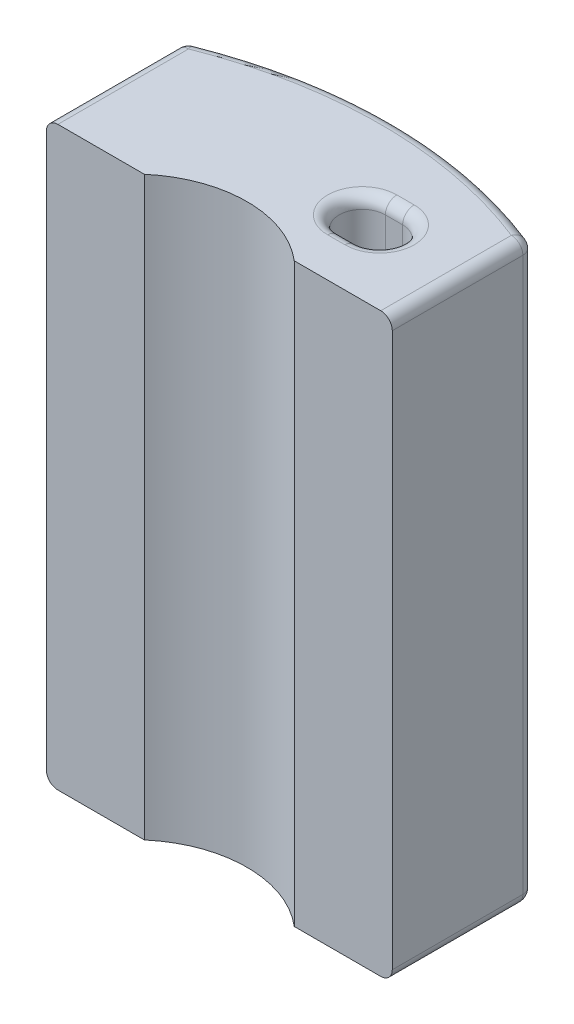
SolidWorks part; units mm, degrees
ref_plane "Front Plane" through (0, 0, 0) normal (0, 0, 1) x (1, 0, 0)
ref_plane "Top Plane" through (0, 0, 0) normal (0, 1, 0) x (1, 0, 0)
ref_plane "Right Plane" through (0, 0, 0) normal (1, 0, 0) x (0, 0, -1)
sketch "Sketch1" plane through (0, 0, 0) normal (0, 1, 0) x (1, 0, 0)
  line L0 (-15, 2) -> (15, 2) construction
  line L1 (-15, 2) -> (-15, -10)
  line L2 (-15, -10) -> (-6.4992, -10)
  line L3 (15, 2) -> (15, -10)
  line L4 (15, -10) -> (6.4992, -10)
  line L5 (0, 0) -> (0, -17.6) construction
  line L6 (-8.9, 0) -> (8.9, 0) construction
  line L7 (-8.9, 0) -> (-8.9, -1.6) construction
  line L8 (-8.9, -1.6) -> (8.9, -1.6) construction
  line L9 (8.9, 0) -> (8.9, -1.6) construction
  line L10 (0, 0) -> (0, 5) construction
  line L11 (-9.5, 2) -> (-9.5, -4.6) construction
  line L12 (-9.5, -4.6) -> (-7, -4.6) construction
  line L13 (-7, -4.6) -> (-7, -5.6) construction
  line L14 (-7, -5.6) -> (7, -5.6) construction
  line L15 (7, -5.6) -> (7, -4.6) construction
  line L16 (7, -4.6) -> (9.5, -4.6) construction
  line L17 (9.5, -4.6) -> (9.5, 2) construction
  line L18 (9.5, 2) -> (15, 2) construction
  line L19 (-15, 2) -> (-9.5, 2) construction
  line L20 (0, 0) -> (0, -5.6) construction
  line L21 (-9.5, 2) -> (-15, 2) construction
  line L22 (9.5, 2) -> (15, 2) construction
  line L23 (0, -5.6) -> (0, -7.6) construction
  arc A0 (-6.4992, -10) -> (6.4992, -10) centre (0, -17.6) cw
  arc A1 (-15, 2) -> (15, 2) centre (0, -34) cw
  dimension "D4" = 10
  dimension "D7" = 3
  dimension "D1" = 1.6
  dimension "D2" = 17.8
  dimension "D3" = 4
  dimension "D5" = 2
  dimension "D6" = 30
  dimension "D8" = 1
  dimension "D9" = 19
  dimension "D10" = 2
  dimension "D11" = 15
  dimension "D12" = 14
extrude "Boss-Extrude1" add sketch "Sketch1" along normal mid plane 50
sketch "Sketch3" plane through (0, 0, 0) normal (0, 1, 0) x (1, 0, 0)
  line L0 (-9.5, 2) -> (-9.5, 0.9321)
  line L3 (-9.5, -5.6) -> (9.5, -5.6)
  line L7 (9.5, -5.6) -> (9.5, -2.5321)
  line L8 (-9.5, 2) -> (-9.5, 15.755)
  line L9 (-9.5, 15.755) -> (9.5, 15.755)
  line L10 (9.5, 15.755) -> (9.5, 2)
  line L11 (-7, -5.6) -> (7, -5.6) construction
  line L12 (-9.5, -2.5321) -> (-9.5, -5.6)
  line L13 (9.5, 0.9321) -> (9.5, 2)
  line L14 (-8.5, -0.8) -> (8.5, -0.8) construction
  arc A0 (10.055, 5.7) -> (-10.055, 5.7) centre (0, 5.7) ccw construction
  arc A1 (-9.5, -2.5321) -> (-9.5, 0.9321) centre (-8.5, -0.8) cw
  arc A2 (9.5, 0.9321) -> (9.5, -2.5321) centre (8.5, -0.8) cw
  dimension "D1" = 2
  dimension "D2" = 17
  dimension "D3" = 0.8
extrude "Cut-Extrude1" cut sketch "Sketch3" against normal mid plane 40
sketch "Sketch4" plane through (0, 0, 5.6) normal (0, 0, -1) x (-1, 0, 0)
  line L1 (-9.5, 20) -> (9.5, 20) construction
  line L2 (-4, 20) -> (0.5205, 20)
  line L4 (0, 0) -> (15, 0) construction
  line L5 (15, 25) -> (15, -25) construction
  line L6 (0.5205, -20) -> (0.5205, -11.274)
  line L7 (-4, -20) -> (0.5205, -20)
  line L8 (-4, -15.24) -> (-4, -20)
  line L9 (-4, 20) -> (-4, -15.24)
  line L10 (0.5205, -11.274) -> (0.5205, 20)
  circle A0 centre (0, 15.24) radius 2.4
  arc A1 (-4, 15.24) -> (0.5205, 11.274) centre (0, 15.24) ccw construction
  arc A2 (-4, -15.24) -> (0.5205, -11.274) centre (0, -15.24) cw construction
  circle A3 centre (0, -15.24) radius 2.4
  dimension "D1" = 4.8
  dimension "D2" = 8
extrude "Boss-Extrude2" add sketch "Sketch4" along normal blind 4 rebuild error yes
sketch "Sketch5" plane through (0, 25, 0) normal (0, 1, 0) x (1, 0, 0)
  line L0 (7.5, -3.6) -> (6, -3.6) construction
  line L1 (7.5, -5.6) -> (6, -5.6)
  line L2 (7.5, -1.6) -> (6, -1.6)
  line L7 (9.5, -5.6) -> (9.5, -2.5321) construction
  arc A0 (7.5, -5.6) -> (7.5, -1.6) centre (7.5, -3.6) ccw
  arc A1 (6, -1.6) -> (6, -5.6) centre (6, -3.6) ccw
  point P2 (6.75, -3.6)
extrude "Cut-Extrude2" cut sketch "Sketch5" against normal blind 22
fillet "Fillet1" radius 4 2 edges at (-9.5, 0, -3.8253) (9.5, 0, -3.8253)
fillet "Fillet2" radius 1 13 edges at (4, 25, 3.6) (6.75, 25, 1.6) (9.5, 25, 3.6) (-1.75, 20, 5.6) (-9.5, 0, 5.6) (0, -20, 5.6) (9.5, 0, 5.6) (8.5, 20, 5.6) (6.75, 25, 5.6) (9.5, 0, -0.9321) (-9.5, 0, -0.9321) (-9.5, 0, 2.5321) (9.5, 0, 2.5321)
fillet "Fillet3" radius 1 10 edges at (0, 20, -5) (0, -20, -5) (0, 25, -5) (-15, 25, 4) (15, 25, 4) (15, 0, -2) (15, -25, 4) (-15, -25, 4) (0, -25, -5) (-15, 0, -2)
